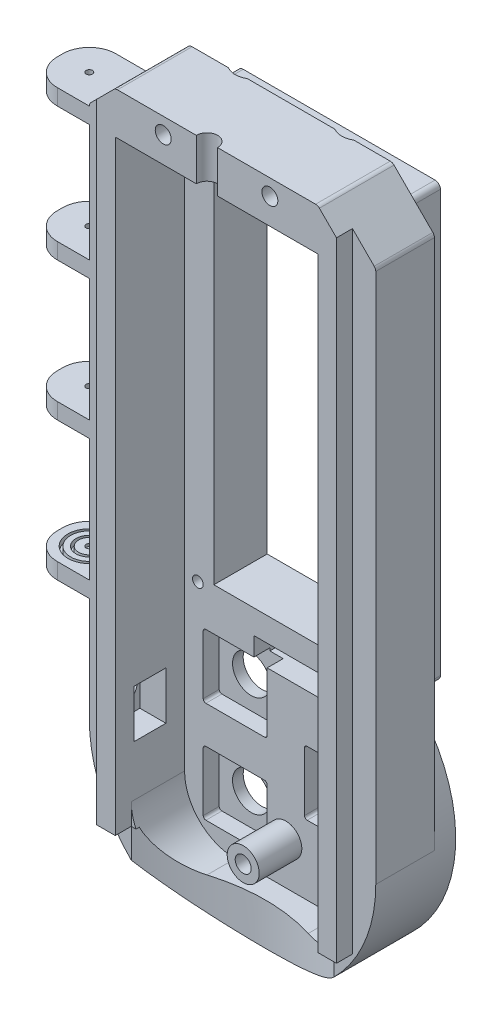
SolidWorks part; units mm, degrees
ref_plane "Alzado" through (0, 0, 0) normal (0, 0, 1) x (1, 0, 0)
ref_plane "Planta" through (0, 0, 0) normal (0, 1, 0) x (1, 0, 0)
ref_plane "Vista lateral" through (0, 0, 0) normal (1, 0, 0) x (0, 0, -1)
sketch "Croquis1" plane through (0, 0, 0) normal (0, 0, 1) x (1, 0, 0)
  line L1 (-19, -40.5) -> (19, -40.5)
  line L2 (-19, -40.5) -> (-19, 40.5)
  line L3 (-19, 40.5) -> (19, 40.5)
  line L4 (19, -40.5) -> (19, 40.5)
  line L5 (-19, -40.5) -> (19, 40.5) construction
  line L6 (-19, 40.5) -> (19, -40.5) construction
  line L7 (-19, -40.5) -> (19, -40.5)
  line L8 (-19, -40.5) -> (-19, -78.5)
  line L9 (-19, -78.5) -> (19, -78.5)
  line L10 (19, -40.5) -> (19, -78.5)
  line L13 (-13.5, 36) -> (13.5, 36)
  line L28 (13.5, 36) -> (13.5, -36)
  line L29 (-13.5, 36) -> (-13.5, -36)
  line L30 (-13.5, -36) -> (13.5, -36)
  circle A0 centre (-9.5, -50) radius 3.5
  circle A1 centre (9.5, -59.5) radius 3.5
  circle A2 centre (-9.5, -69) radius 3.5
  arc A3 (19, -40.5) -> (-19, -40.5) centre (0, -59.5) cw
  point P0 (0, 0)
  point P27 (9.5, -63)
  point P30 (9.5, -54.5)
  point P34 (-13.5, 0)
extrude "Saliente-Extruir1" add sketch "Croquis1" along normal blind 5 contours L1 L4 L3 L2 L30 L29 L13 L28 | L10 L1 L8 L9 A2 A1 A0 | A3 L10 | A3 L9 | A3 L8 region at (-18.1053, 0, 0) region at (0.2752, -59.5, 0) region at (-22.1912, -59.5, 0) region at (22.1912, -59.5, 0) region at (0, -81.6912, 0)
sketch "Croquis2" plane through (0, 0, 0) normal (0, 0, -1) x (-1, 0, 0)
  line L0 (-19, 40.5) -> (19, 40.5)
  line L1 (19, -40.5) -> (-19, -40.5)
  line L2 (-19, -40.5) -> (-19, 40.5)
  line L4 (19, -40.5) -> (19, 40.5)
  line L5 (-13.5, 36) -> (-13.5, -36)
  line L7 (-13.5, -36) -> (13.5, -36)
  line L8 (13.5, -36) -> (13.5, 36)
  line L9 (13.5, 36) -> (-13.5, 36)
extrude "Saliente-Extruir2" add sketch "Croquis2" along normal blind 5
sketch "Croquis3" plane through (0, 0, 5) normal (0, 0, 1) x (1, 0, 0)
  line L0 (26.8701, -59.5) -> (26.8701, 40.5)
  line L1 (19, -59.5) -> (19, 40.5)
  line L2 (19, 40.5) -> (-19, 40.5)
  line L3 (-19, 40.5) -> (-19, -59.5)
  line L4 (26.8701, 40.5) -> (19, 48.3701)
  line L5 (19, 48.3701) -> (-19, 48.3701)
  line L6 (-19, 48.3701) -> (-26.8701, 40.5)
  line L7 (-26.8701, 40.5) -> (-26.8701, -59.5)
  arc A2 (-19, -59.5) -> (19, -59.5) centre (0, -59.5) ccw
  arc A3 (-26.8701, -59.5) -> (26.8701, -59.5) centre (0, -59.5) ccw
extrude "Saliente-Extruir9" add sketch "Croquis3" against normal blind 1
sketch "Croquis4" plane through (0, 0, 4) normal (0, 0, -1) x (-1, 0, 0)
  line L0 (-19, 40.5) -> (-19, -40.5)
  line L1 (-19, 40.5) -> (19, 40.5)
  line L2 (19, 40.5) -> (19, -40.5)
  line L3 (14, -77) -> (-14, -77)
  line L4 (-19, -72) -> (-19, -41.338)
  line L5 (19, -72) -> (19, -40.5)
  line L6 (-26.8701, 40.5) -> (-19, 48.3701)
  line L7 (-19, 48.3701) -> (19, 48.3701)
  line L8 (19, 48.3701) -> (26.8701, 40.5)
  line L9 (26.8701, 40.5) -> (26.8701, -59.5)
  line L10 (-26.8701, 40.5) -> (-26.8701, -59.5)
  arc A0 (-19, -40.5) -> (-26.8701, -59.5) centre (0, -59.5) ccw construction
  arc A1 (-14, -77) -> (-19, -72) centre (-14, -72) cw
  arc A2 (14, -77) -> (19, -72) centre (14, -72) ccw
  arc A3 (-19, -40.5) -> (19, -40.5) centre (0, -59.5) ccw construction
  arc A4 (-26.8701, -59.5) -> (26.8701, -59.5) centre (0, -59.5) ccw
  arc M1 (19, -40.5) -> (26.8701, -59.5) centre (0, -59.5) cw
  line M2 (26.8701, -59.5) -> (26.8701, 40.5)
  line M3 (26.8701, 40.5) -> (19, 48.3701)
  line M4 (19, 48.3701) -> (-19, 48.3701)
  line M5 (-19, 48.3701) -> (-26.8701, 40.5)
  line M6 (-26.8701, 40.5) -> (-26.8701, -59.5)
  arc M7 (-26.8701, -59.5) -> (-19, -40.5) centre (0, -59.5) cw
  line M8 (-19, -40.5) -> (-19, 40.5)
  line M9 (-19, 40.5) -> (19, 40.5)
  line M10 (19, 40.5) -> (19, -40.5)
  dimension "D1" = 5
extrude "Saliente-Extruir10" add sketch "Croquis4" against normal blind 11 contours M10 M1 M2 M3 M4 M5 M6 M7 M8 M9 region at (20.2052, 0, 4)
sketch "Croquis5" plane through (0, 0, 5) normal (0, 0, 1) x (1, 0, 0)
  line L0 (-19, -59.5) -> (-19, -69)
  line L1 (19, -69) -> (19, -59.5)
  line L2 (9.5, -78.5) -> (-9.5, -78.5)
  line L3 (19, -59.5) -> (19, -40.5)
  line L4 (-19, -59.5) -> (-19, -40.5)
  arc A0 (-19, -40.5) -> (19, -40.5) centre (0, -59.5) ccw
  arc A1 (-9.5, -78.5) -> (-19, -69) centre (-9.5, -69) cw
  arc A2 (9.5, -78.5) -> (19, -69) centre (9.5, -69) ccw
extrude "Saliente-Extruir11" add sketch "Croquis5" along normal blind 10
fillet "Redondeo1" radius 1 4 edges at (-19, -40.5, -2.5) (-19, 40.5, -0.5) (19, 40.5, -0.5) (19, -40.5, -2.5)
fillet "Redondeo2" radius 1 5 edges at (-18.7071, 40.2071, 4) (18.7071, 40.2071, 4) (-19, -0.5, 4) (0, 40.5, 4) (19, -0.5, 4)
fillet "Redondeo3" radius 1 4 edges at (-26.8701, 40.5, 9.5) (-19, 48.3701, 9.5) (26.8701, 40.5, 9.5) (19, 48.3701, 9.5)
sketch "Croquis6" plane through (-26.8701, 0, 0) normal (-1, 0, 0) x (0, 0, 1)
  line L2 (8.5, -50.5) -> (14.5, -50.5)
  line L3 (14.5, -50.5) -> (14.5, -59.5)
  line L4 (14.5, -59.5) -> (8.5, -59.5)
  line L5 (8.5, -50.5) -> (8.5, -59.5)
extrude "Cortar-Extruir1" cut sketch "Croquis6" against normal blind 8
sketch "Croquis7" plane through (-26.8701, 0, 0) normal (-1, 0, 0) x (0, 0, 1)
  line L0 (8.5, -50.5) -> (14.5, -50.5)
  line L1 (14.5, -50.5) -> (14.5, -59.5)
  line L2 (14.5, -59.5) -> (8.5, -59.5)
  line L3 (8.5, -59.5) -> (8.5, -50.5)
  circle A0 centre (11.5, -55) radius 2.5
extrude "Saliente-Extruir12" add sketch "Croquis7" against normal blind 3
sketch "Croquis8" plane through (-26.8701, 0, 0) normal (-1, 0, 0) x (0, 0, 1)
  line L0 (4, 40.0858) -> (4, 37.0858)
  line L1 (4, 39.5) -> (4, -41.5556) construction
  line L2 (4, 37.0858) -> (15, 37.0858)
  line L3 (15, -59.5) -> (15, 40.0858) construction
  line L4 (15, 37.0858) -> (15, 40.0858)
  line L5 (15, 40.0858) -> (4, 40.0858)
  line L6 (9.5, 37.0858) -> (9.5, 15.0858)
  line L7 (9.5, 15.0858) -> (15, 15.0858)
  line L8 (9.5, 15.0858) -> (4, 15.0858)
  line L9 (4, 15.0858) -> (4, 12.0858)
  line L10 (4, 40.0858) -> (4, -59.5) construction
  line L11 (4, 12.0858) -> (15, 12.0858)
  line L12 (15, 12.0858) -> (15, 15.0858)
  line L13 (9.5, 12.0858) -> (9.5, -10.9142)
  line L14 (9.5, -10.9142) -> (15, -10.9142)
  line L15 (15, -10.9142) -> (15, -13.9142)
  line L16 (15, -13.9142) -> (4, -13.9142)
  line L17 (4, -13.9142) -> (4, -10.9142)
  line L18 (4, -10.9142) -> (9.5, -10.9142)
  line L19 (9.5, -13.9142) -> (9.5, -36.9142)
  line L20 (9.5, -36.9142) -> (15, -36.9142)
  line L21 (15, -36.9142) -> (15, -39.9142)
  line L22 (15, -39.9142) -> (4, -39.9142)
  line L23 (4, -39.9142) -> (4, -36.9142)
  line L24 (4, -36.9142) -> (9.5, -36.9142)
  line M2 (15, -59.5) -> (15, 40.0858)
  line M3 (15, 40.0858) -> (4, 40.0858)
  line M4 (4, 40.0858) -> (4, -59.5)
extrude "Saliente-Extruir13" add sketch "Croquis8" along normal blind 11 contours L2 M4 M2 M3 | L11 L7 L8 M4 M2 | L18 L16 L14 M4 M2 | L24 L22 L20 M4 M2 region at (-26.8701, 38.5858, 9.5) region at (-26.8701, 13.5858, 9.5) region at (-26.8701, -12.4142, 9.5) region at (-26.8701, -38.4142, 9.5)
fillet "Redondeo4" radius 5 8 edges at (-37.8701, -38.4142, 4) (-37.8701, -38.4142, 15) (-37.8701, -12.4142, 4) (-37.8701, -12.4142, 15) (-37.8701, 13.5858, 4) (-37.8701, 13.5858, 15) (-37.8701, 38.5858, 4) (-37.8701, 38.5858, 15)
sketch "Croquis9" plane through (0, 40.0858, 0) normal (0, 1, 0) x (1, 0, 0)
  circle A0 centre (-32.3701, -9.5) radius 0.6
extrude "Cortar-Extruir2" cut sketch "Croquis9" against normal blind 80
sketch "Croquis10" plane through (0, -39.9142, 0) normal (0, -1, 0) x (1, 0, 0)
  circle A0 centre (-32.3701, 9.5) radius 0.6
extrude "Saliente-Extruir14" add sketch "Croquis10" against normal blind 2.5
sketch "Croquis11" plane through (0, -36.9142, 0) normal (0, 1, 0) x (1, 0, 0)
  circle A0 centre (-32.3701, -9.5) radius 2
  circle A1 centre (-32.3701, -9.5) radius 2.5
  circle A2 centre (-32.3701, -9.5) radius 3.5
  circle A3 centre (-32.3701, -9.5) radius 4
extrude "Cortar-Extruir3" cut sketch "Croquis11" against normal blind 1 contours A3 A2 | A1 A0 region at (-34.7993, -36.9142, 9.5) region at (-36.2569, -36.9142, 9.5)
sketch "Croquis13" plane through (0, 0, 15) normal (0, 0, 1) x (1, 0, 0)
  line L0 (19, 40.5) -> (22.5, 40.5)
  line L1 (19, -69) -> (22.5, -69)
  line L2 (22.5, -69) -> (22.5, 40.5)
  line L3 (19, -69) -> (19, 40.5)
  line L5 (22.5, 40.5) -> (22.5, 44.8701)
  line L6 (-19, -69) -> (-19, 40.5)
  line L7 (-22.5, -69) -> (-22.5, 40.5)
  line L8 (-19, -69) -> (-22.5, -69)
  line L9 (-19, 40.5) -> (-22.5, 40.5)
  line L10 (-19, -69) -> (-19, -65.5)
  line L12 (19, -65.5) -> (19, -69)
  line L13 (-22.5, 40.5) -> (-22.5, 44.8701)
  line L14 (-26.5772, 40.7929) -> (-19.2929, 48.0772) construction
  line L15 (-22.5, 44.8701) -> (-19.2929, 48.0772)
  line L16 (-18.5858, 48.3701) -> (18.5858, 48.3701)
  line L19 (22.5, 44.8701) -> (19.2929, 48.0772)
  arc A0 (-19.2929, 48.0772) -> (-18.5858, 48.3701) centre (-18.5858, 47.3701) cw
  arc A1 (19.2929, 48.0772) -> (18.5858, 48.3701) centre (18.5858, 47.3701) ccw
  line M1 (19, 40.5) -> (19, -69)
  line M5 (-19, -69) -> (-19, 40.5)
  line M6 (-19, 40.5) -> (19, 40.5)
  line M14 (26.5772, 40.7929) -> (19.2929, 48.0772)
  arc M15 (19.2929, 48.0772) -> (18.5858, 48.3701) centre (18.5858, 47.3701) ccw
  line M16 (18.5858, 48.3701) -> (-18.5858, 48.3701)
  arc M17 (-18.5858, 48.3701) -> (-19.2929, 48.0772) centre (-18.5858, 47.3701) ccw
  line M18 (-19.2929, 48.0772) -> (-26.5772, 40.7929)
extrude "Saliente-Extruir15" add sketch "Croquis13" along normal blind 3 contours L6 L9 L7 L8 M5 | L1 L2 L0 L3 M1 | L13 L9 L0 L5 M6 M14 M15 M16 M17 M18 region at (0, 44.3353, 15) region at (20.75, -14.25, 15) region at (-20.75, -14.25, 15)
sketch "Croquis14" plane through (0, 0, 4) normal (0, 0, -1) x (-1, 0, 0)
  circle A0 centre (10, 45.3701) radius 1.5
  circle A1 centre (-10, 45.3701) radius 1.5
extrude "Cortar-Extruir4" cut sketch "Croquis14" against normal blind 14
sketch "Croquis16" plane through (0, -69, 0) normal (0, -1, 0) x (-1, 0, 0)
  line L1 (22.5, -15) -> (19, -15)
  line L2 (22.5, -15) -> (22.5, -18)
  line L3 (22.5, -18) -> (19, -18)
  line L4 (-19, -15) -> (-22.5, -15)
  line L5 (-19, -15) -> (-19, -18)
  line L6 (-19, -18) -> (-22.5, -18)
  line L7 (-22.5, -15) -> (-22.5, -18)
  line L8 (19, -15) -> (19, -18)
extrude "Saliente-Extruir16" add sketch "Croquis16" along normal blind 4
sketch "Croquis25" plane through (0, 0, 18) normal (0, 0, 1) x (1, 0, 0)
  line L0 (-10, 45.3701) -> (10, 45.3701)
  line L1 (0, 45.3701) -> (0, -70.6299)
  circle A0 centre (0, -70.6299) radius 3
  circle A1 centre (0, -70.6299) radius 1.5
extrude "Saliente-Extruir21" add sketch "Croquis25" against normal blind 18 contours A1 A0 region at (2.0613, -68.5686, 18)
sketch "Croquis26" plane through (0, 0, 18) normal (0, 0, 1) x (1, 0, 0)
  circle A0 centre (0, -70.6299) radius 1.5
extrude "Cortar-Extruir7" cut sketch "Croquis26" against normal blind 18
sketch "Croquis28" plane through (0, 0, 5) normal (0, 0, 1) x (1, 0, 0)
  circle A0 centre (-16.5, 38) radius 1
  circle A1 centre (14.5, 38) radius 1
  circle A2 centre (14.5, -37) radius 1
  circle A3 centre (-16.5, -37) radius 1
extrude "Cortar-Extruir8" cut sketch "Croquis28" against normal blind 4
sketch "Croquis34" plane through (0, -73, 0) normal (0, -1, 0) x (1, 0, 0)
  line L0 (19, 15) -> (-19, 15)
  arc A0 (-19, 15) -> (19, 15) centre (0, 41.3676) ccw
extrude "Cortar-Extruir12" cut sketch "Croquis34" along normal blind 20
sketch "Croquis29" plane through (0, 0, 18) normal (0, 0, 1) x (1, 0, 0)
  circle A0 centre (0, -70.6299) radius 1.5
  circle A1 centre (0, -70.6299) radius 3
extrude "Cortar-Extruir9" cut sketch "Croquis29" against normal blind 5
sketch "Croquis30" plane through (0, 0, 18) normal (0, 0, 1) x (1, 0, 0)
  line L3 (-1.8, 45.3701) -> (-1.8, 40.5)
  line L5 (-19, 40.5) -> (19, 40.5) construction
  line L6 (-1.8, 40.5) -> (0.2, 40.5)
  line L8 (0.2, 40.5) -> (0.2, 48.3701)
  line L9 (18.5858, 48.3701) -> (-18.5858, 48.3701) construction
  line L10 (0.2, 48.3701) -> (-1.8, 48.3701)
  line L11 (-1.8, 48.3701) -> (-1.8, 45.3701)
revolve "Cortar-Revolución1" cut sketch "Croquis30" angle 360 about L3
sketch "Croquis31" plane through (0, 0, 5) normal (0, 0, 1) x (1, 0, 0)
  line L3 (-6, -40.5) -> (-6, -44.5)
  line L4 (-6, -44.5) -> (10, -44.5)
  line L5 (10, -44.5) -> (10, -40.5)
  line L6 (10, -40.5) -> (-6, -40.5)
extrude "Cortar-Extruir10" cut sketch "Croquis31" against normal up to surface (5 mm away) up to face at (1.5, -70.6299, 0)
sketch "Croquis32" plane through (0, 0, 5) normal (0, 0, 1) x (1, 0, 0)
  line L0 (-3.5, -50) -> (-3.5, -44.5)
  line L1 (-4, -44) -> (-15, -44)
  line L2 (-15.5, -44.5) -> (-15.5, -55.5)
  line L3 (-15, -56) -> (-4, -56)
  line L4 (-3.5, -55.5) -> (-3.5, -50)
  line L5 (-9.5, -63) -> (-4, -63)
  line L6 (-3.5, -63.5) -> (-3.5, -74.5)
  line L7 (-4, -75) -> (-15, -75)
  line L8 (-15.5, -74.5) -> (-15.5, -63.5)
  line L9 (-15, -63) -> (-9.5, -63)
  line L10 (15.5, -59.5) -> (15.5, -54)
  line L11 (15, -53.5) -> (4, -53.5)
  line L12 (3.5, -54) -> (3.5, -65)
  line L13 (4, -65.5) -> (15, -65.5)
  line L14 (15.5, -65) -> (15.5, -59.5)
  arc A0 (15.5, -54) -> (15, -53.5) centre (15, -54) ccw
  arc A1 (15, -65.5) -> (15.5, -65) centre (15, -65) ccw
  arc A2 (3.5, -65) -> (4, -65.5) centre (4, -65) ccw
  arc A3 (4, -53.5) -> (3.5, -54) centre (4, -54) ccw
  arc A4 (-4, -63) -> (-3.5, -63.5) centre (-4, -63.5) cw
  arc A5 (-3.5, -74.5) -> (-4, -75) centre (-4, -74.5) cw
  arc A6 (-15, -75) -> (-15.5, -74.5) centre (-15, -74.5) cw
  arc A7 (-15.5, -63.5) -> (-15, -63) centre (-15, -63.5) cw
  arc A8 (-4, -56) -> (-3.5, -55.5) centre (-4, -55.5) ccw
  arc A9 (-3.5, -44.5) -> (-4, -44) centre (-4, -44.5) ccw
  arc A10 (-15.5, -55.5) -> (-15, -56) centre (-15, -55.5) ccw
  arc A11 (-15, -44) -> (-15.5, -44.5) centre (-15, -44.5) ccw
  point P40 (-15.5, -56)
  dimension "D1" = 0.5
extrude "Cortar-Extruir11" cut sketch "Croquis32" against normal blind 3
sketch "Croquis35" plane through (0, 0, 13) normal (0, 0, 1) x (1, 0, 0)
  line L0 (-1.8392, -73) -> (1.8392, -73)
  circle A0 centre (0, -70.6299) radius 3
  line M3 (-1.8392, -73) -> (1.8392, -73)
extrude "Saliente-Extruir22" add sketch "Croquis35" against normal blind 8 contours A0 M3 region at (0, -73.2544, 13)
sketch "Croquis36" plane through (0, 0, 0) normal (0, 0, -1) x (-1, 0, 0)
  line L4 (7.375, -42.7165) -> (9.625, -44.0155)
  line L5 (10, -43.799) -> (10, -41.201)
  line L6 (9.625, -40.9845) -> (7.375, -42.2835)
  arc A0 (10, -41.201) -> (9.625, -40.9845) centre (9.75, -41.201) ccw
  arc A1 (9.625, -44.0155) -> (10, -43.799) centre (9.75, -43.799) ccw
  arc A2 (7.375, -42.2835) -> (7.375, -42.7165) centre (7.5, -42.5) ccw
  dimension "D1" = 0.25
extrude "Cortar-Extruir13" cut sketch "Croquis36" against normal blind 1
chamfer "Chaflán1" distance 2 angle 45 3 edges at (-11.5, 45.3701, 4) (11.5, 45.3701, 4) (1.5, -70.6299, 0)
